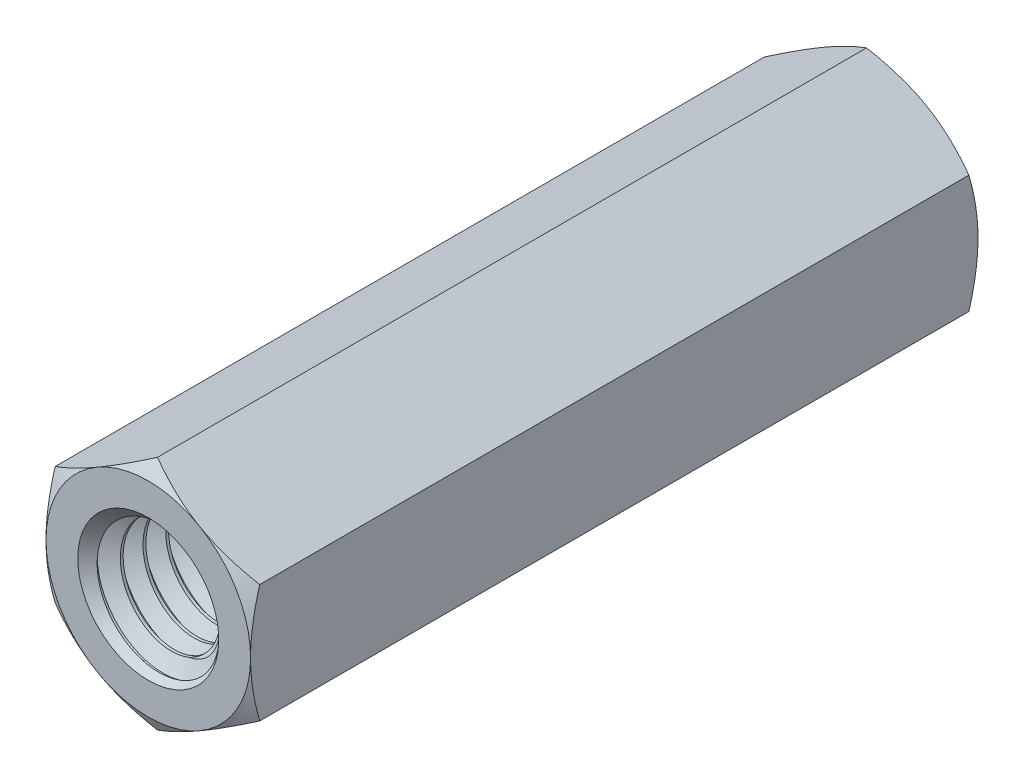
SolidWorks part; units mm, degrees
ref_plane "Front Plane" through (0, 0, 0) normal (0, 0, 1) x (1, 0, 0)
ref_plane "Top Plane" through (0, 0, 0) normal (0, 1, 0) x (1, 0, 0)
ref_plane "Right Plane" through (0, 0, 0) normal (1, 0, 0) x (0, 0, -1)
sketch "Sketch3" plane through (0, 0, 0) normal (1, 0, 0) x (0, 0, -1)
  line L0 (-8, 0) -> (8, 0) construction
  line L1 (0, 2.25) -> (0, -2.25) construction
  line L2 (-8, 1.5) -> (-8, -1.5) construction
  point P2 (3.2, 0)
  point P3 (-3.2, 0)
  dimension "D1" = 4.8
  dimension "Length" = 16
  dimension "Min Thread Length" = 4.8
  dimension "Thread Dia" = 3
  dimension "Hex" = 4.5
sketch "Sketch1" plane through (0, 0, 0) normal (0, 0, 1) x (1, 0, 0)
  line L1 (0, 2.5981) -> (-2.25, 1.299)
  line L2 (-2.25, 1.299) -> (-2.25, -1.299)
  line L3 (-2.25, -1.299) -> (0, -2.5981)
  line L4 (0, -2.5981) -> (2.25, -1.299)
  line L5 (2.25, -1.299) -> (2.25, 1.299)
  line L6 (2.25, 1.299) -> (0, 2.5981)
  circle A0 centre (0, 0) radius 2.25 construction
  circle A1 centre (0, 0) radius 1.5
extrude "Extrude1" add sketch "Sketch1" along normal up to vertex (8 mm away) and the other way up to vertex (8 mm away) up to point (0, 0, 8) other way up to point (0, 0, -8)
sketch "Sketch11" plane through (0, 0, -8) normal (0, 0, -1) x (-1, 0, 0)
  circle A0 centre (0, 0) radius 1.5 construction
  circle A1 centre (0, 0) radius 1.5
curve "Helix/Spiral1" pitch 0.5 height 16.5 turns 33 parameters "Pitch"=0.5
sketch "Sketch12" plane through (0, 0, 0) normal (1, 0, 0) x (0, 0, -1)
  line L0 (8.4375, 1.5) -> (8, 1.5)
  line L1 (8.4375, 1.5) -> (8.25, 1.1752)
  line L2 (8.25, 1.1752) -> (8.1875, 1.1752)
  line L3 (8.1875, 1.1752) -> (8, 1.5)
  line L4 (8.2188, 1.1752) -> (8.2188, 1.5) construction
  line L5 (8.3438, 1.3376) -> (8.0938, 1.3376) construction
  dimension "D1" = 0.0625
  dimension "D2" = 0.25
  dimension "D3" = 60
sweep "Sweep1" add profiles "Sketch12" path "Helix/Spiral1"
sketch "Sketch6" plane through (0, 0, -8) normal (0, 0, -1) x (-1, 0, 0)
  line L6 (0, 2.5981) -> (-2.25, 1.299)
  line L7 (-2.25, 1.299) -> (-2.25, -1.299)
  line L8 (-2.25, -1.299) -> (0, -2.5981)
  line L9 (0, -2.5981) -> (2.25, -1.299)
  line L10 (2.25, -1.299) -> (2.25, 1.299)
  line L11 (2.25, 1.299) -> (0, 2.5981)
  line L12 (0, 2.5981) -> (-2.25, 1.299)
  line L13 (-2.25, 1.299) -> (-2.25, -1.299)
  line L14 (-2.25, -1.299) -> (0, -2.5981)
  line L15 (0, -2.5981) -> (2.25, -1.299)
  line L16 (2.25, -1.299) -> (2.25, 1.299)
  line L17 (2.25, 1.299) -> (0, 2.5981)
  dimension "D1" = 0
extrude "Extrude2" cut sketch "Sketch6" along normal through all
sketch "Sketch7" plane through (0, 0, -8) normal (0, 0, -1) x (-1, 0, 0)
  circle A2 centre (0, 0) radius 1.5508
  circle A3 centre (0, 0) radius 1.5508
  dimension "D1" = 0.0508
extrude "Extrude3" cut sketch "Sketch7" against normal through all draft 43
sketch "Sketch8" plane through (0, 0, -8) normal (0, 0, -1) x (-1, 0, 0)
  circle A0 centre (0, 0) radius 2.25 construction
  circle A1 centre (0, 0) radius 2.25
extrude "Extrude4" cut sketch "Sketch8" against normal through all draft 60 flip side to cut
mirror "Mirror1" about plane through (0, 0, 0) normal (0, 0, 1) of "Extrude2", "Extrude3", "Extrude4"
sketch "Sketch9" [suppressed] plane through (0, 0, 0) normal (1, 0, 0) x (0, 0, -1)
  line L1 (-1.2, 1.1353) -> (1.2, 1.1353)
  line L2 (-1.2, 1.1353) -> (-1.2, 0)
  line L3 (-1.2, 0) -> (1.2, 0)
  line L4 (1.2, 1.1353) -> (1.2, 0)
  line L7 (-6, 0) -> (6, 0) construction
revolve "Revolve" [suppressed] add sketch "Sketch9" angle 360 about L0
sketch "Sketch10" [suppressed] plane through (0, 0, 0) normal (1, 0, 0) x (0, 0, -1)
  line L0 (6, 1.25) -> (1.2, 1.25)
  line L1 (-6, 1.25) -> (-1.2, 1.25)
  line L2 (1.2, 1.25) -> (1.2, -1.25)
  line L3 (-6, -1.25) -> (-1.2, -1.25)
  line L4 (-1.2, 1.25) -> (-1.2, -1.25)
  line L5 (1.2, -1.25) -> (6, -1.25)
equation "\"D1@Sketch3\" = \"Min Thread Length@Sketch3\""
equation "\"D3@Helix/Spiral1\" = \"Length@Sketch3\"+\"Pitch@Helix/Spiral1\""
equation "\"D1@Sketch12\" = \"Pitch@Helix/Spiral1\"*.125"
equation "\"D2@Sketch12\" = \"Pitch@Helix/Spiral1\"*.5"
